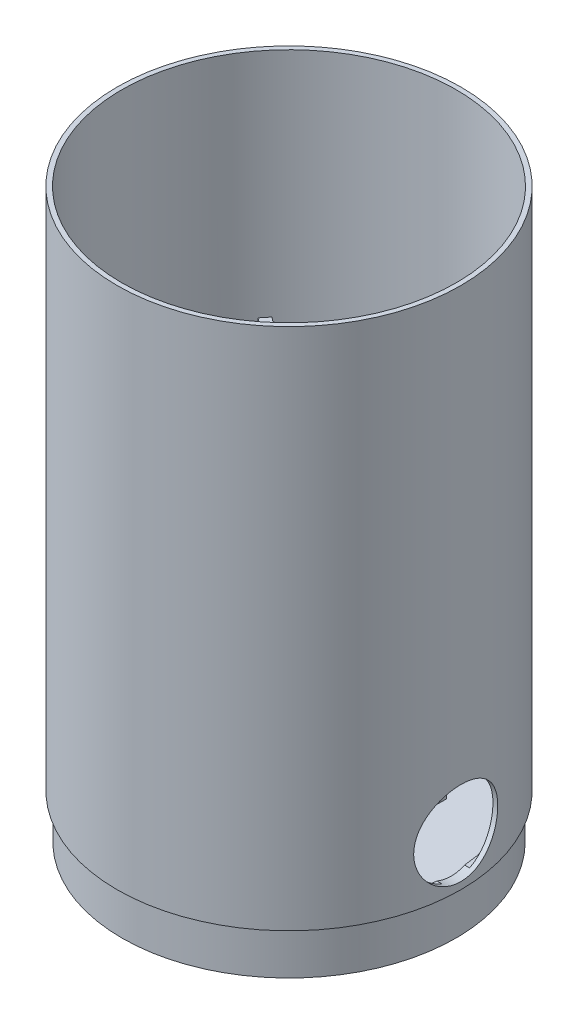
SolidWorks part; units mm, degrees
ref_plane "Front Plane" through (0, 0, 0) normal (0, 0, 1) x (1, 0, 0)
ref_plane "Top Plane" through (0, 0, 0) normal (0, 1, 0) x (1, 0, 0)
ref_plane "Right Plane" through (0, 0, 0) normal (1, 0, 0) x (0, 0, -1)
sketch "Sketch1" plane through (0, 0, 0) normal (0, 1, 0) x (1, 0, 0)
  circle A0 centre (0, 0) radius 35.75
  circle A1 centre (0, 0) radius 34.75
  dimension "D1" = 71.5
  dimension "D2" = 1
extrude "Boss-Extrude1" add sketch "Sketch1" along normal blind 9.5
sketch "Sketch3" plane through (0, 0, 0) normal (0, -1, 0) x (1, 0, 0)
  circle A2 centre (0, 0) radius 34.75 construction
  circle A3 centre (0, 0) radius 34.75
extrude "Boss-Extrude2" add sketch "Sketch3" against normal blind 2
sketch "Sketch4" plane through (0, 2, 0) normal (0, 1, 0) x (1, 0, 0)
  line L0 (0, 34.75) -> (0, -34.75) construction
  line L1 (-34.75, 0) -> (34.75, 0) construction
  line L2 (-27.5772, 22.75) -> (-27.5772, -22.75)
  line L3 (-26.5772, 21.75) -> (9.9228, 21.75)
  line L4 (-26.5772, 21.75) -> (-26.5772, -21.75)
  line L5 (-26.5772, -21.75) -> (9.9228, -21.75)
  line L6 (9.9228, 21.75) -> (9.9228, -21.75)
  line L7 (-26.5772, 21.75) -> (9.9228, -21.75) construction
  line L8 (-26.5772, -21.75) -> (9.9228, 21.75) construction
  line L9 (-27.5772, -22.75) -> (10.9228, -22.75)
  line L10 (10.9228, 22.75) -> (10.9228, -22.75)
  line L11 (-27.5772, 22.75) -> (10.9228, 22.75)
  circle A0 centre (0, 0) radius 34.75 construction
  circle A1 centre (0, 0) radius 34.75 construction
  circle A2 centre (0, 0) radius 35.75 construction
  point P9 (-8.3272, 0)
  dimension "D1" = 36.5
  dimension "D2" = 43.5
  dimension "D4" = 1
extrude "Boss-Extrude3" add sketch "Sketch4" along normal blind 70
sketch "Sketch2" plane through (0, 9.5, 0) normal (0, 1, 0) x (1, 0, 0)
  circle A0 centre (0, 0) radius 36.8
  circle A1 centre (0, 0) radius 34.75 construction
  circle A2 centre (0, 0) radius 34.75
  dimension "D1" = 73.6
extrude "Boss-Extrude4" add sketch "Sketch2" along normal blind 2
sketch "Sketch5" plane through (0, 11.5, 0) normal (0, 1, 0) x (1, 0, 0)
  circle A0 centre (0, 0) radius 36.8 construction
  circle A1 centre (0, 0) radius 36.8
  circle A2 centre (0, 0) radius 35.8
  dimension "D1" = 1
extrude "Boss-Extrude5" add sketch "Sketch5" along normal blind 110
sketch "Sketch6" plane through (0, 72, 0) normal (0, 1, 0) x (1, 0, 0)
  line L0 (-26.2679, 22.75) -> (-27.0616, 23.4374)
  line L1 (-27.5772, 21.1439) -> (-28.4104, 21.7827)
  line L2 (-27.5772, 21.1439) -> (-26.2679, 22.75)
  line L3 (0, 0) -> (-45.7469, 0) construction
  line L4 (-26.2679, -22.75) -> (-27.0616, -23.4374)
  line L5 (-27.5772, -21.1439) -> (-26.2679, -22.75)
  line L6 (-27.5772, -21.1439) -> (-28.4104, -21.7827)
  circle A0 centre (0, 0) radius 35.8 construction
  circle A1 centre (0, 0) radius 35.8 construction
  arc A2 (-27.0616, 23.4374) -> (-28.4104, 21.7827) centre (0, 0) ccw
  arc A3 (-27.0616, -23.4374) -> (-28.4104, -21.7827) centre (0, 0) cw
extrude "Boss-Extrude6" add sketch "Sketch6" against normal up to surface (60.5 mm away) up to face at (-18.1666, 11.5, 0)
ref_plane "Plane1" through (36.8, 0, 0) normal (1, 0, 0) x (0, 0, -1)
sketch "Sketch7" plane through (36.8, 0, 0) normal (1, 0, 0) x (0, 0, -1)
  circle A0 centre (0, 20) radius 9
  dimension "D1" = 18
  dimension "D2" = 20
extrude "Cut-Extrude1" cut sketch "Sketch7" against normal blind 5
sketch "Sketch8" plane through (0, 72, 0) normal (0, 1, 0) x (1, 0, 0)
  line L0 (9.9228, 21.75) -> (19.4271, 31.2543) construction
  line L1 (10.2764, 21.3964) -> (19.7806, 30.9007)
  line L2 (9.5693, 22.1036) -> (18.7823, 31.3165)
  line L3 (9.5693, 22.1036) -> (10.2764, 21.3964)
  line L4 (19.7806, 30.9007) -> (18.7823, 31.3165)
  line L5 (0, 0) -> (42.2423, 0) construction
  line L6 (9.5693, 22.1036) -> (19.0735, 31.6078) construction
  line L7 (9.5693, -22.1036) -> (10.2764, -21.3964)
  line L8 (10.2764, -21.3964) -> (19.7806, -30.9007)
  line L9 (19.7806, -30.9007) -> (18.7823, -31.3165)
  line L10 (9.5693, -22.1036) -> (18.7823, -31.3165)
  circle A1 centre (0, 0) radius 36.8 construction
  dimension "D1" = 0.5
  dimension "D2" = 0.5
extrude "Boss-Extrude7" add sketch "Sketch8" against normal blind 50
